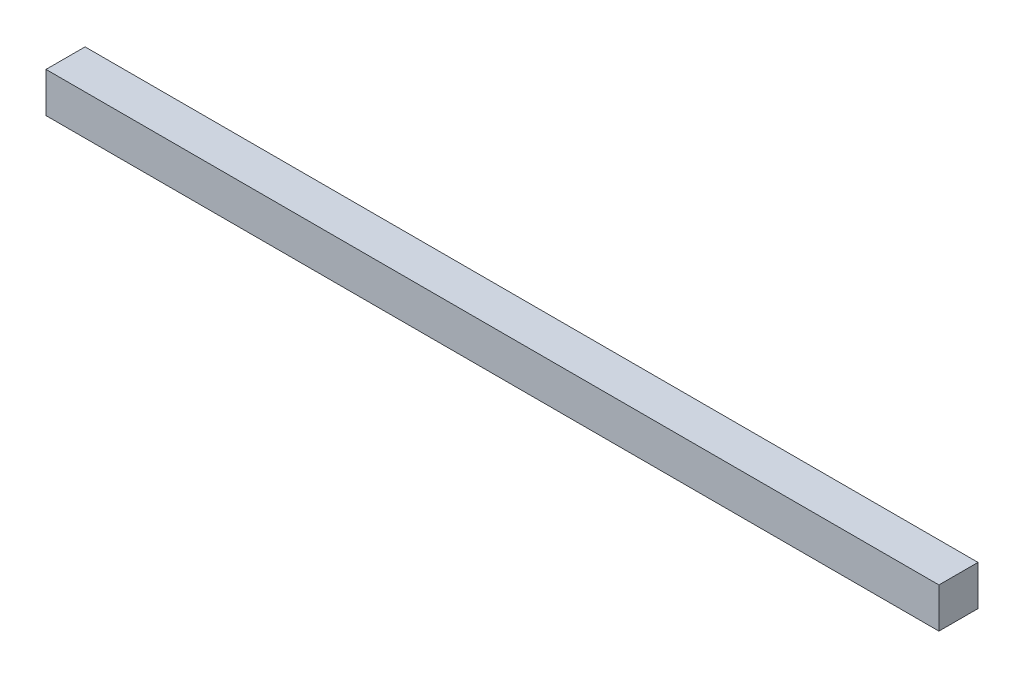
SolidWorks part; units mm, degrees
ref_plane "Спереди" through (0, 0, 0) normal (0, 0, 1) x (1, 0, 0)
ref_plane "Сверху" through (0, 0, 0) normal (0, 1, 0) x (1, 0, 0)
ref_plane "Справа" through (0, 0, 0) normal (1, 0, 0) x (0, 0, -1)
other "Configuration Table"
sketch "Ширина_фанера_плюс_зазор" plane through (0, 0, 0) normal (0, 0, 1) x (1, 0, 0)
  line L0 (-0.1, -3.075) -> (137.075, -3.075)
  line L1 (137.075, -3.075) -> (137.075, 3.075)
  line L2 (137.075, 3.075) -> (-0.1, 3.075)
  line L3 (-0.1, 3.075) -> (-0.1, -3.075)
  line L4 (-0.1, -3.075) -> (137.075, 3.075) construction
  point P4 (68.4875, 0)
  dimension "Ширина" = 137.175
  dimension "Глубина" = 6.15
  dimension "Положение_ПоОси" = 68.4875
extrude "Прямой_участок" add sketch "Ширина_фанера_плюс_зазор" along normal blind 6
equation "\"D1@Прямой_участок\" = \"Толщина тонких панелей\""
equation "\"Глубина@Ширина_фанера_плюс_зазор\"  = \"Толщина горизонтальных плит\"+\"Посадочный зазор\""
equation "\"Фанера\"= \"Толщина горизонтальных плит\""
equation "\"Ширина шипа\"=16"
equation "\"Межосевое шипов\"=40"
equation "\"Посадочный зазор\"=0.15"
equation "\"Основная фреза\"=6"
equation "\"Мелкая фреза\"=6"
equation "\"Запас разгрузки\"=0.05"
equation "\"Ширина образца\"=84"
equation "\"Высота образца\"=50"
equation "\"Канал М6\"=6"
equation "\"Гайка под ключ\"=10.3"
equation "\"Длина кармана гайки\"=6.2"
equation "\"Отступ гайки\"=12"
equation "\"Ширина@Ширина_фанера_плюс_зазор\" = (\"Глубина ячейки\"+3*\"Толщина тонких панелей\")/2+(\"Толщина вертикальных стенок\"+\"Посадочный зазор\")/2+0.1"
equation "\"Положение_ПоОси@Ширина_фанера_плюс_зазор\" = (\"Глубина ячейки\"+3*\"Толщина тонких панелей\")/4+(\"Толщина вертикальных стенок\"+\"Посадочный зазор\")/4-0.05"
equation "\"Ширина груза\"= 160"
equation "\"Глубина груза\"= 240"
equation "\"Высота груза\"= 160"
equation "\"Ширина ячейки\"= \"Ширина груза\" + 10"
equation "\"Глубина ячейки\"= \"Глубина груза\" + 10"
equation "\"Высота ячейки\"= \"Высота груза\" + 10 + 13"
equation "\"Колво ячеек ширина\"= 2"
equation "\"Колво ячеек высота\"= 2"
equation "\"Толщина стенки\" = \"Толщина тонких панелей\""
equation "\"Крепление дверцы\"= 5 "
equation "\"Ширина рейки\"= \"Толщина шестерни\""
equation "\"Высота рейки\"= 20"
equation "\"Высота пола\" = 2*\"Толщина тонких панелей\""
equation "\"Колво полозьев\"= 5"
equation "\"Отступ рейки\"= 20"
equation "\"Глубина каретки\"= \"Глубина ячейки\" + 30 + \"Мотор Y высота корпуса\" + 20 + \"Удлинение платформы по глубине\""
equation "\"Длинна рейки\" = (\"Ширина ячейки\"+\"Толщина вертикальных стенок\"+\"Крепление дверцы\")*\"Колво ячеек ширина\"+\"Ширина ячейки выгрузки\"*\"Колво выгрузки\"+\"Толщина вертикальных стенок\"+2*\"Отступ крепления мотора фиксации\"-\"Крепление дверцы\"*\"Колво ячеек ширина\""
equation "\"Отступ шпильки\"= 26"
equation "\"Диаметр шпильки\"= 5"
equation "\"Длинна шпильки\" = (\"Высота ячейки\"+\"Толщина горизонтальных плит\"+\"Высота пола\")*\"Колво ячеек высота\"+2*(\"Толщина горизонтальных плит\"+\"Отступ рейки\")"
equation "\"Ширина пластины\" = 50"
equation "\"Высота зона выгрузки\"= \"Высота ячейки\" * 2 + \"Толщина стенки\" * 2"
equation "\"Колво выгрузки\"= 1"
equation "\"Ширина ячейки выгрузки\" = \"Ширина ячейки\"+\"Толщина вертикальных стенок\"+2*\"Отступ крепления мотора фиксации\""
equation "\"Отступ крепления мотора фиксации\" = (70-\"Толщина вертикальных стенок\")/2"
equation "\"Мотор X ширина корпуса\"= 42.3"
equation "\"Мотор X высота корпуса\"= 42.3"
equation "\"Мотор X длина корпуса\"= 40"
equation "\"Мотор X вылет вала\"= 19.8"
equation "\"Мотор Y ширина корпуса\"= 42.3"
equation "\"Мотор Y высота корпуса\"= 42.3"
equation "\"Мотор Y длина корпуса\"= 48"
equation "\"Мотор Y вылет вала\"= 30"
equation "\"Мотор Z ширина корпуса\"= 42"
equation "\"Мотор Z высота корпуса\"= 42"
equation "\"Мотор Z длина корпуса\"= 40"
equation "\"Мотор Z вылет вала\"= 23"
equation "\"Мотор диаметр вала ПРЕДВ\"= 5"
equation "\"Мотор шаг крепления ПРЕДВ\"= 31"
equation "\"Мотор диаметр отверстий ПРЕДВ\"= 3"
equation "\"Мотор глубина отверстий ПРЕДВ\"= 4.5"
equation "\"Мотор диаметр буртика ПРЕДВ\"= 22"
equation "\"Мотор высота буртика ПРЕДВ\"= 2"
equation "\"Мотор диаметр шкива ПРЕДВ\"= 16"
equation "\"Мотор длина шкива ПРЕДВ\"= 12"
equation "\"Мотор отступ шкива ПРЕДВ\"= 5"
equation "\"Мотор X шаг градусов\"= 1.8"
equation "\"Мотор Y шаг градусов\"= 1.8"
equation "\"Мотор Z шаг градусов\"= 1.8"
equation "\"Мотор Y диаметр ротора\"= 25.78"
equation "\"Толщина шестерни\"= 10"
equation "\"Толщина тонких панелей\" = 6"
equation "\"Толщина вертикальных стенок\" = 6"
equation "\"Толщина горизонтальных плит\" = 6"
equation "\"Базовая высота корпуса\"= (\"Высота ячейки\"+\"Толщина тонких панелей\"+\"Высота пола\")*\"Колво ячеек высота\"+6*\"Толщина тонких панелей\"+\"Мотор X ширина корпуса\"+\"Мотор Y ширина корпуса\"+75"
equation "\"Высота корпуса\"= (\"Высота ячейки\"+\"Толщина горизонтальных плит\"+\"Высота пола\")*\"Колво ячеек высота\"+2*\"Толщина горизонтальных плит\"+4*\"Толщина тонких панелей\"+\"Мотор X ширина корпуса\"+\"Мотор Y ширина корпуса\"+75"
equation "\"Смещение центра корпуса\"= (\"Высота корпуса\"-\"Базовая высота корпуса\")/2-(\"Толщина горизонтальных плит\"-\"Толщина тонких панелей\")"
equation "\"Отметка пола\"= -\"Базовая высота корпуса\"/2+\"Толщина тонких панелей\""
equation "\"Отметка потолка\"= \"Отметка пола\"+\"Высота корпуса\"-2*\"Толщина горизонтальных плит\""
equation "\"Отметка верхней полки\"= \"Отметка потолка\"-(28+\"Толщина тонких панелей\")-\"Высота ячейки\"-\"Высота пола\""
equation "\"Отметка нижней полки\"= \"Отметка верхней полки\"-\"Высота ячейки\"-\"Высота пола\"-\"Толщина горизонтальных плит\""
